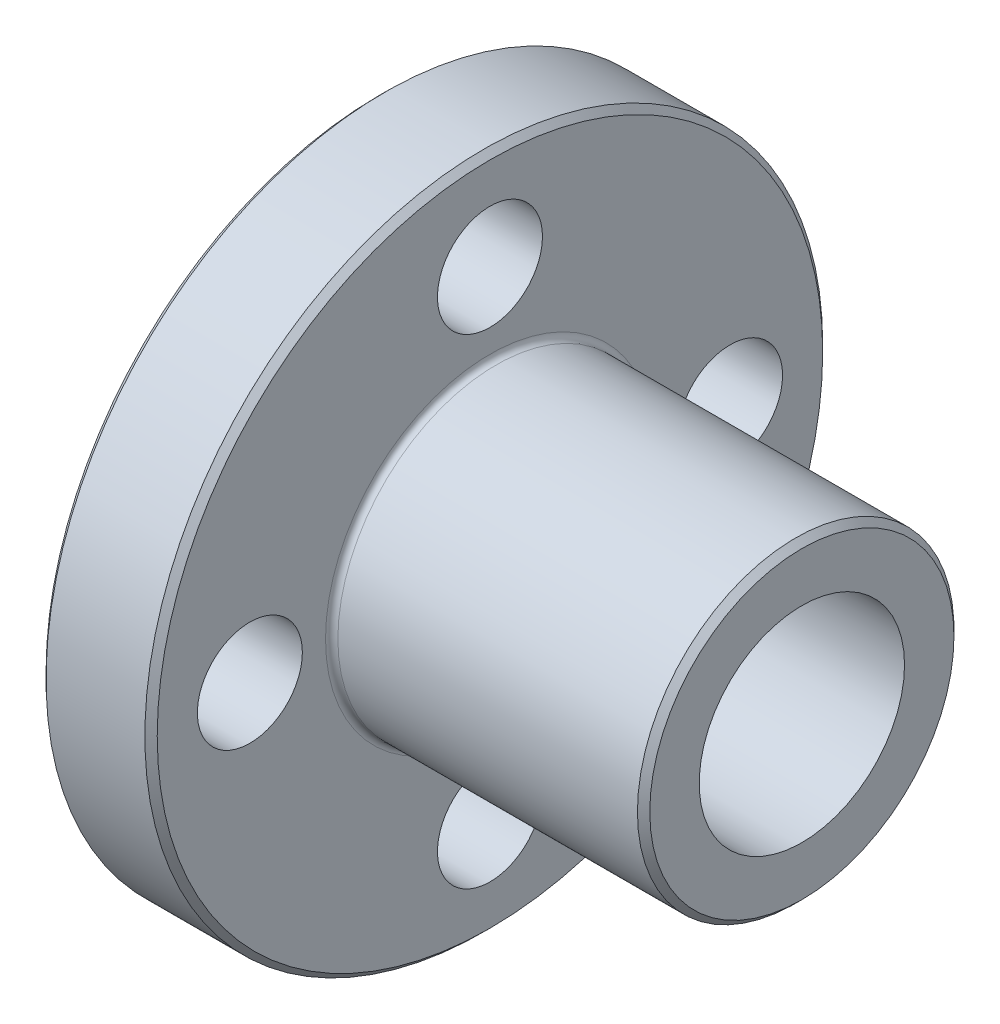
SolidWorks part; units mm, degrees
ref_plane "Front Plane" through (0, 0, 0) normal (0, 0, 1) x (1, 0, 0)
ref_plane "Top Plane" through (0, 0, 0) normal (0, 1, 0) x (1, 0, 0)
ref_plane "Right Plane" through (0, 0, 0) normal (1, 0, 0) x (0, 0, -1)
sketch "Sketch1" plane through (0, 0, 0) normal (1, 0, 0) x (0, 0, -1)
  line L0 (0, 55) -> (0, -55) construction
  line L1 (55, 0) -> (-55, 0) construction
  line L2 (0, 26.5276) -> (0, -17.5827) construction
  line L3 (-24.9497, 0) -> (25.2758, 0) construction
  circle A0 centre (0, 0) radius 10.975
  circle A1 centre (0, 7.775) radius 1.7
  circle A2 centre (7.775, 0) radius 1.7
  circle A3 centre (0, -7.775) radius 1.7
  circle A4 centre (-7.775, 0) radius 1.7
  dimension "D1" = 21.95
  dimension "D2" = 3.4
  dimension "D3" = 7.775
  dimension "D4" = 7.775
extrude "Boss-Extrude1" add sketch "Sketch1" along normal blind 3.6
sketch "Sketch2" plane through (0, 0, 0) normal (1, 0, 0) x (0, 0, -1)
  circle A0 centre (0, 0) radius 5.125
  dimension "D1" = 10.25
extrude "Boss-Extrude2" add sketch "Sketch2" along normal blind 13.7
extrude "Boss-Extrude3" add sketch "Sketch2<2>" along normal blind 13.7 and the other way blind 1.3
sketch "Sketch2<2>" plane through (0, 0, 0) normal (1, 0, 0) x (0, 0, -1) same geometry as "Sketch2"
sketch "Sketch3" plane through (0, 0, 0) normal (1, 0, 0) x (0, 0, -1)
  circle A0 centre (0, 0) radius 3.325
  dimension "D1" = 6.65
extrude "Cut-Extrude1" cut sketch "Sketch3" against normal through all both and the other way through all
fillet "Fillet1" radius 0.2 1 edges at (3.6, 0, -5.125)
chamfer "Chamfer1" distance 0.2 angle 45 3 edges at (13.7, 0, -5.125) (0, 0, -10.975) (3.6, 0, -10.975)
